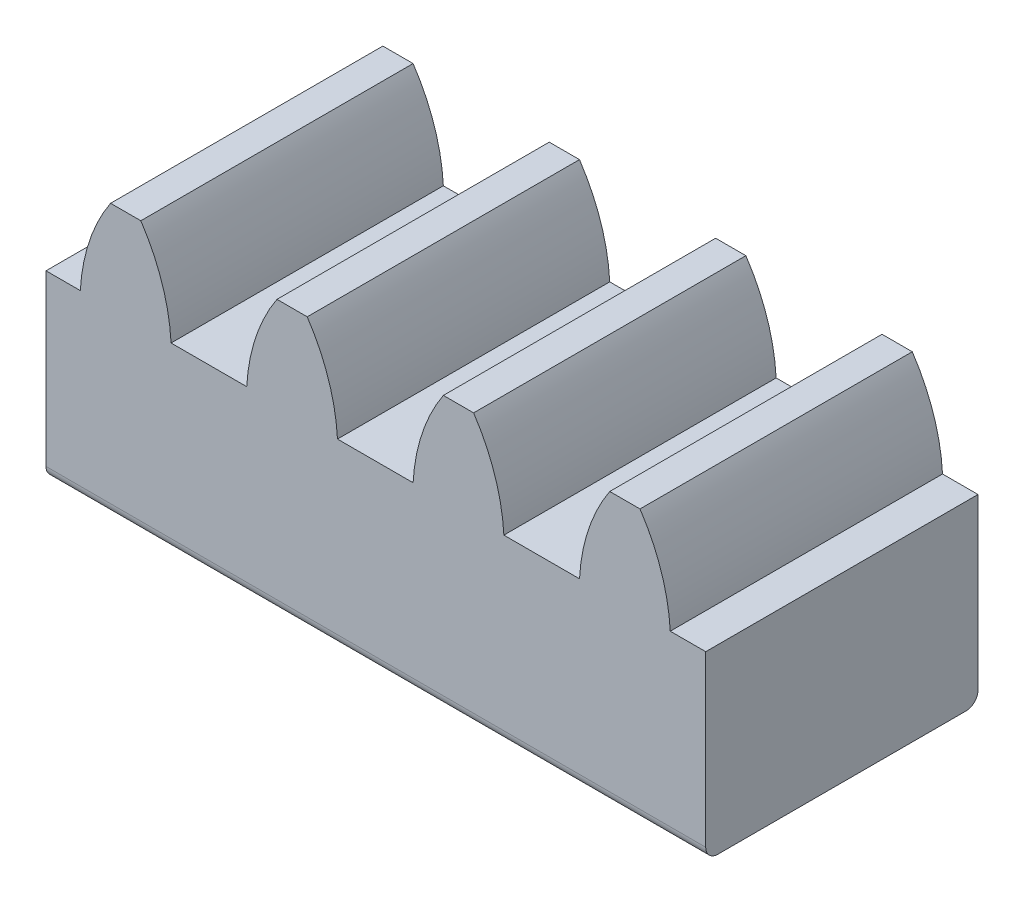
SolidWorks part; units mm, degrees
ref_plane "Front Plane" through (0, 0, 0) normal (0, 0, 1) x (1, 0, 0)
ref_plane "Top Plane" through (0, 0, 0) normal (0, 1, 0) x (1, 0, 0)
ref_plane "Right Plane" through (0, 0, 0) normal (1, 0, 0) x (0, 0, -1)
sketch "Sketch1" plane through (0, 0, 0) normal (0, 0, 1) x (1, 0, 0)
  line L0 (-55.8407, -27.8293) -> (-55.8407, -33.8096) construction
  line L1 (-60.6927, -40.8293) -> (39.3073, -40.8293)
  line L2 (-60.6927, -40.8293) -> (-60.6927, -34.8293)
  line L3 (-60.6927, -34.8293) -> (39.3073, -34.8293)
  line L4 (39.3073, -40.8293) -> (39.3073, -34.8293)
  line L5 (-56.3407, -31.8293) -> (-55.3407, -31.8293)
  line L6 (12.3073, -36.8293) -> (1.3073, -36.8293) construction
  line L7 (-35.6927, -19.8293) -> (-35.6927, -31.8293) construction
  arc A3 (-57.3407, -34.8293) -> (-56.3407, -31.8293) centre (-51.3498, -35.1596) cw
  arc A5 (-54.3407, -34.8293) -> (-55.3407, -31.8293) centre (-60.3316, -35.1596) ccw
  dimension "D3" = 2
  dimension "D4" = 6
  dimension "D1" = 100
  dimension "D2" = 6
  dimension "D5" = 1
  dimension "D6" = 1
  dimension "D7" = 3
  dimension "D8" = 25
extrude "Boss-Extrude1" add sketch "Sketch1" against normal up to surface (9 mm away) contours L1 L4 L3 L2 region at (-10.6927, -37.8293, 0)
extrude "Boss-Extrude2" add sketch "Sketch1<3>" against normal up to surface (9 mm away) contours L3 A5 L5 A3 | A3 L3 | L3 A5 region at (-55.8407, -33.5433, 0) up to face at (-10.6927, -37.8293, -9)
sketch "Sketch1<3>" plane through (0, 0, 0) normal (0, 0, 1) x (1, 0, 0) same geometry as "Sketch1"
pattern_linear "LPattern1" count 6 spacing 5.5 along (1, 0, 0) of "Boss-Extrude2"
sketch "Sketch2" plane through (0, -40.8293, 0) normal (0, -1, 0) x (1, 0, 0)
  line L0 (-60.6927, -9) -> (-60.6927, 0) construction
  line L1 (-60.6927, -14.5) -> (-75.6927, -14.5)
  line L2 (-60.6927, -14.5) -> (-60.6927, 5.5)
  line L3 (-60.6927, 5.5) -> (-75.6927, 5.5)
  line L4 (-75.6927, -14.5) -> (-75.6927, 5.5)
  line L5 (39.3073, -9) -> (39.3073, 0) construction
  point P8 (39.3073, -4.5)
  point P9 (-60.6927, -4.5)
  dimension "D1" = 15
  dimension "D2" = 20
extrude "Boss-Extrude3" add sketch "Sketch2" against normal blind 5
fillet "Fillet1" radius 10 1 edges at (-60.6927, -35.8293, -4.5)
fillet "Fillet2" radius 3 4 edges at (-60.6927, -38.3293, -14.5) (-75.6927, -38.3293, -14.5) (-75.6927, -38.3293, 5.5) (-60.6927, -38.3293, 5.5)
sketch "Sketch3" plane through (39.3073, 0, 0) normal (1, 0, 0) x (0, 0, -1)
  line L4 (11, -32.8293) -> (-2, -32.8293)
  line L12 (-2, -40.8293) -> (11, -40.8293)
  line L13 (11.5, -40.8293) -> (9, -40.8293) construction
  line L14 (0, -40.8293) -> (-2.5, -40.8293) construction
  line L16 (11, -42.8293) -> (11, -32.8293)
  line L18 (-2, -32.8293) -> (-2, -42.8293)
  line L19 (-2, -42.8293) -> (11, -42.8293)
  line L20 (11, -40.8293) -> (11, -32.8293)
  line L22 (-2, -32.8293) -> (-2, -40.8293)
  line L23 (11, -32.8293) -> (-2, -32.8293)
  dimension "D1" = 2
extrude "Boss-Extrude4" add sketch "Sketch3" along normal blind 5
sketch "Sketch4" plane through (0, 0, 2) normal (0, 0, 1) x (1, 0, 0)
  line L1 (39.3073, -40.8293) -> (42.3073, -40.8293)
  line L2 (39.3073, -40.8293) -> (39.3073, -32.8293)
  line L3 (39.3073, -32.8293) -> (42.3073, -32.8293)
  line L4 (42.3073, -40.8293) -> (42.3073, -32.8293)
  dimension "D1" = 3
  dimension "D2" = 8
extrude "Boss-Extrude5" add sketch "Sketch4" along normal blind 5
fillet "Fillet3" radius 0.4 29 edges at (-74.814, -40.8293, -13.6213) (-75.6927, -40.8293, -4.5) (-74.814, -40.8293, 4.6213) (-68.1927, -40.8293, 5.5) (-61.5713, -40.8293, 4.6213) (-60.6927, -40.8293, 1.25) (-10.6927, -40.8293, 0) (39.3073, -40.8293, 3.5) (41.8073, -40.8293, -11) (39.3073, -40.8293, -10) (-10.6927, -40.8293, -9) (-60.6927, -40.8293, -10.25) (-61.5713, -40.8293, -13.6213) (-68.1927, -40.8293, -14.5) (40.8073, -40.8293, 7) (39.3073, -36.8293, 7) (43.3073, -40.8293, 2) (42.3073, -40.8293, 4.5) (42.3073, -36.8293, 7) (42.3073, -36.8293, 2) (44.3073, -36.8293, -11) (44.3073, -40.8293, -4.5) (44.3073, -36.8293, 2) (41.8073, -32.8293, -11) (44.3073, -32.8293, -4.5) (43.3073, -32.8293, 2) (42.3073, -32.8293, 4.5) (40.8073, -32.8293, 7) (39.3073, -32.8293, -2)
hole_wizard "Ø3.0mm Dowel Hole1" positions "3DSketch1" profile "Sketch5" hole size "Ø3.0" standard "ANSI Metric"
sketch3d "3DSketch1"
  line L5 (-72.6927, -40.4293, 5.5) -> (-63.6927, -40.4293, 5.5) construction
  point P0 (-65.6927, -40.8293, 1.5)
  point P2 (-65.6927, -40.8293, -10.5)
  point P4 (-71.6927, -40.8293, -4.492)
  dimension "D1" = 10
  dimension "D2" = 4
  dimension "D3" = 4
  dimension "D4" = 10
  dimension "D5" = 10
  dimension "D6" = 4
sketch "Sketch5" plane through (-65.6927, -40.8293, 1.5) normal (1, 0, 0) x (0, 0, -1)
  line L0 (0, 0) -> (0, 7.8112)
  line L1 (0, 7.8112) -> (1.35, 7)
  line L2 (1.35, 7) -> (1.35, 0)
  line L5 (1.35, 0) -> (0, 0)
  line L10 (0, 7.8112) -> (-1.35, 7) construction
  line L11 (0, -6.35) -> (0, 107.95) construction
  dimension "Hole Dia." = 2.7
  dimension "Hole Depth" = 7
  dimension "Drill Angle" = 118
sketch "Sketch6" plane through (0, 0, 0) normal (0, 0, 1) x (1, 0, 0)
  line L0 (39.7073, -40.8293) -> (-61.0927, -40.8293) construction
  line L1 (-58.4752, -40.8293) -> (-36.6683, -40.8293)
  line L2 (-58.4752, -40.8293) -> (-58.4752, -24.6511)
  line L3 (-58.4752, -24.6511) -> (-36.6683, -24.6511)
  line L4 (-36.6683, -40.8293) -> (-36.6683, -24.6511)
  line L5 (-58.5752, -40.9293) -> (-58.5752, -24.5511)
  line L6 (-58.5752, -24.5511) -> (-36.5683, -24.5511)
  line L7 (-36.5683, -40.9293) -> (-36.5683, -24.5511)
  line L8 (-58.5752, -40.9293) -> (-36.5683, -40.9293)
  dimension "D1" = 0.1
extrude "Cut-Extrude1" cut sketch "Sketch6" against normal through all
delete or keep bodies "Body-Delete/Keep 1" type delete bodies bodies 108 109
